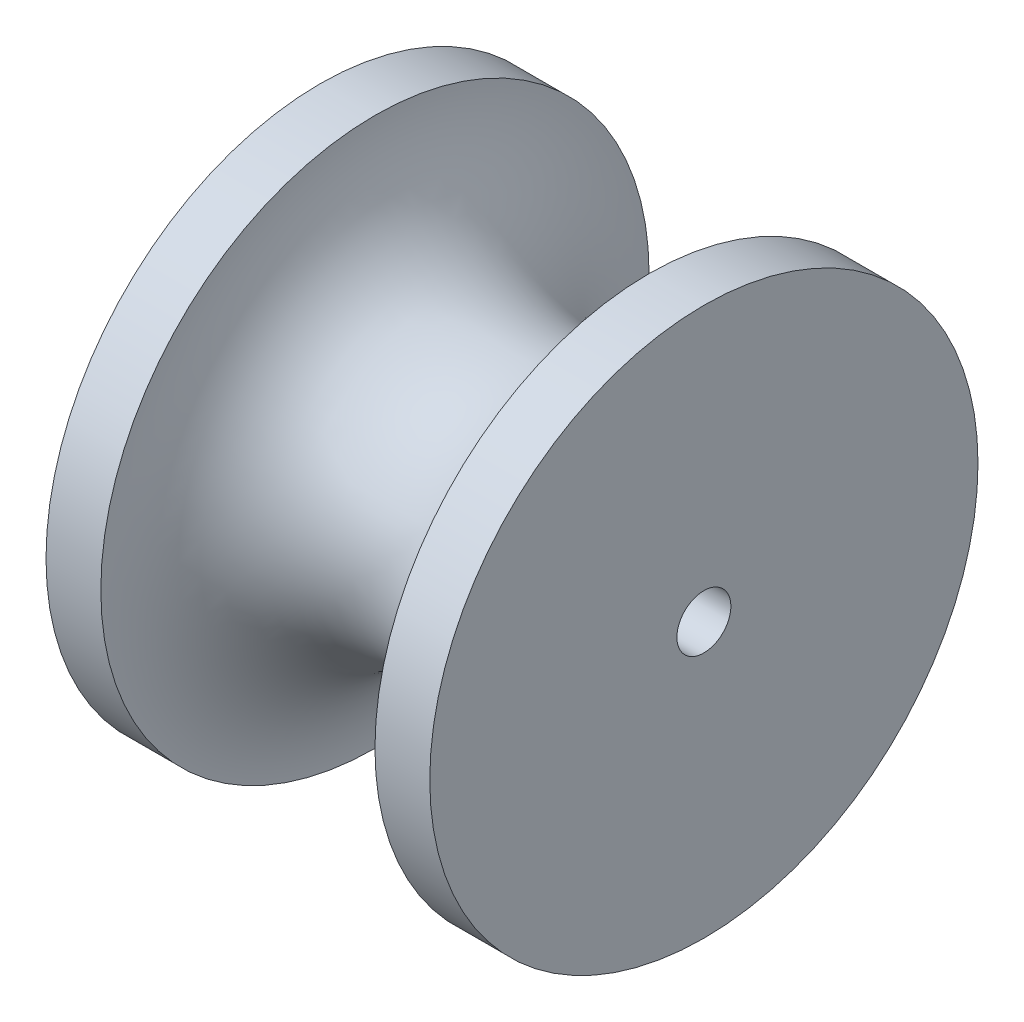
SolidWorks part; units mm, degrees
material "ABS"
ref_plane "Front Plane" through (0, 0, 0) normal (0, 0, 1) x (1, 0, 0)
ref_plane "Top Plane" through (0, 0, 0) normal (0, 1, 0) x (1, 0, 0)
ref_plane "Right Plane" through (0, 0, 0) normal (1, 0, 0) x (0, 0, -1)
sketch "Sketch1" plane through (0, 0, 0) normal (0, 0, 1) x (1, 0, 0)
  line L0 (-35.56, 0) -> (-30.48, 0)
  line L1 (-5.08, 0) -> (0, 0)
  line L2 (-35.56, 0) -> (-35.56, -25.4)
  line L3 (-35.56, -25.4) -> (0, -25.4)
  line L4 (0, -25.4) -> (0, 0)
  arc A0 (-30.48, 0) -> (-5.08, 0) centre (-17.78, 0) ccw
  dimension "D1" = 35.56
  dimension "D3" = 12.7
  dimension "D2" = 25.4
  dimension "D4" = 5.08
revolve "Revolve1" add sketch "Sketch1" angle 360 about L3
sketch "Sketch5" plane through (-35.56, 0, 0) normal (-1, 0, 0) x (0, 0, 1)
  circle A0 centre (0, -25.4) radius 2.5
  circle A2 centre (0, -25.4) radius 25.4 construction
  dimension "D1" = 5
extrude "Cut-Extrude2" cut sketch "Sketch5" against normal blind 35.56
